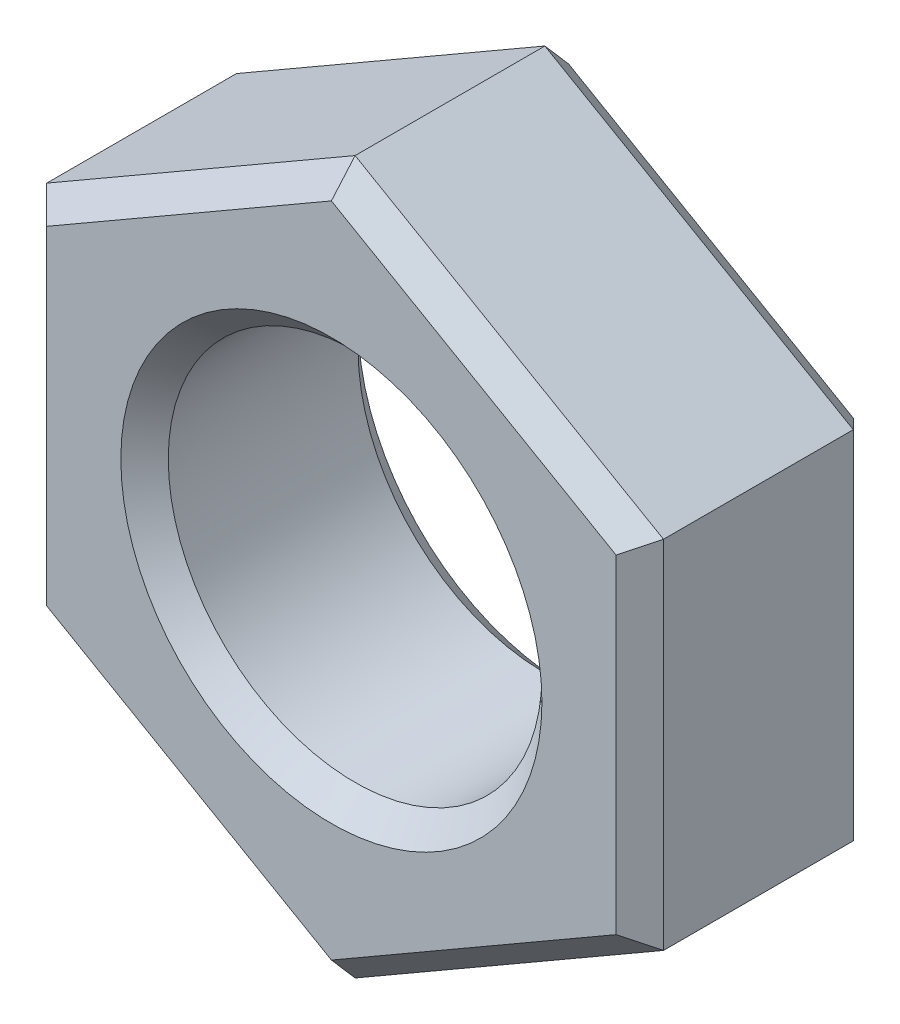
SolidWorks part; units mm, degrees
ref_plane "Front" through (0, 0, 0) normal (0, 0, 1) x (1, 0, 0)
ref_plane "Top" through (0, 0, 0) normal (0, 1, 0) x (1, 0, 0)
ref_plane "Right" through (0, 0, 0) normal (1, 0, 0) x (0, 0, -1)
sketch "Sketch1" plane through (0, 0, 0) normal (0, 0, 1) x (1, 0, 0)
  line L1 (2.6, -1.5011) -> (2.6, 1.5011)
  line L2 (2.6, 1.5011) -> (0, 3.0022)
  line L3 (0, 3.0022) -> (-2.6, 1.5011)
  line L4 (-2.6, 1.5011) -> (-2.6, -1.5011)
  line L5 (-2.6, -1.5011) -> (0, -3.0022)
  line L6 (0, -3.0022) -> (2.6, -1.5011)
  circle A0 centre (0, 0) radius 2.6 construction
  circle A1 centre (0, 0) radius 1.575
  dimension "D1" = 3.15
  dimension "D2" = 5.2
extrude "Boss-Extrude1" add sketch "Sketch1" along normal mid plane 2
chamfer "Deburs" distance 0.2 angle 45 14 edges at (1.575, 0, -1) (2.6, 0, -1) (1.3, 2.2517, -1) (-1.3, 2.2517, -1) (-2.6, 0, -1) (-1.3, -2.2517, -1) (1.3, -2.2517, -1) (1.575, 0, 1) (-1.3, -2.2517, 1) (-2.6, 0, 1) (-1.3, 2.2517, 1) (1.3, 2.2517, 1) (2.6, 0, 1) (1.3, -2.2517, 1)
equation "\"D1@Sketch1\"=\"Hardware Clearance Hole Diameter@Box Assy.Assembly\""
equation "\"D2@Sketch1\"=\"Nut Trap Diameter@Box Assy.Assembly\"-0.3mm"
